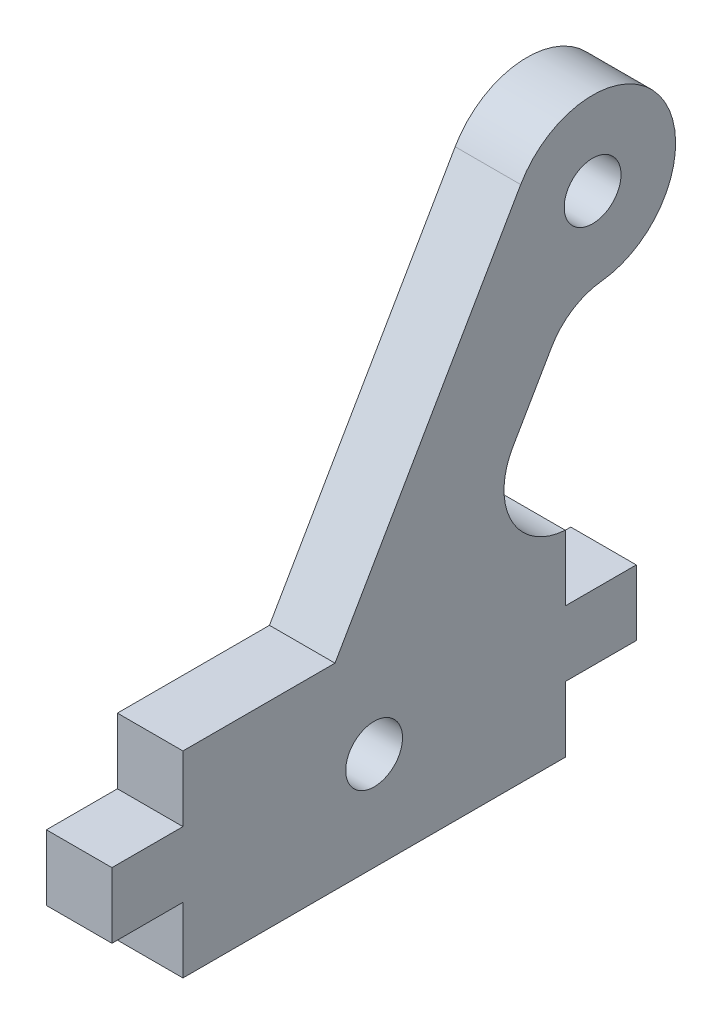
SolidWorks part; units mm, degrees
material "Acrílico (médio-alto impacto)"
ref_plane "Plano frontal" through (0, 0, 0) normal (0, 0, 1) x (1, 0, 0)
ref_plane "Plano superior" through (0, 0, 0) normal (0, 1, 0) x (1, 0, 0)
ref_plane "Plano direito" through (0, 0, 0) normal (1, 0, 0) x (0, 0, -1)
sketch "Principal" plane through (0, 0, 0) normal (1, 0, 0) x (0, 0, -1)
  line L0 (0, 0) -> (10, 17.3205) construction
  line L1 (-12, -1.5) -> (12, -1.5)
  line L2 (-12, -1.5) -> (-12, 1.5)
  line L3 (-12, 1.5) -> (12, 1.5)
  line L4 (12, -1.5) -> (12, 1.5)
  line L5 (0, 1.5) -> (0, -1.5) construction
  line L6 (-12, 0) -> (12, 0) construction
  line L11 (6.7091, 19.2205) -> (-1.7898, 4.5)
  line L12 (-8.75, 1.5) -> (-8.75, 4.5)
  line L13 (-8.75, -4.5) -> (8.75, -4.5)
  line L14 (-8.75, -4.5) -> (-8.75, -1.5)
  line L15 (-8.75, -1.5) -> (8.75, -1.5)
  line L16 (8.75, -4.5) -> (8.75, -1.5)
  line L17 (0, -1.5) -> (0, -4.5) construction
  line L18 (-8.75, -3) -> (8.75, -3) construction
  line L19 (-8.75, 4.5) -> (-1.7898, 4.5)
  line L20 (9.033, 13.6456) -> (3.7528, 4.5)
  line L21 (3.7528, 4.5) -> (8.75, 4.5)
  line L22 (8.75, 4.5) -> (8.75, 1.5)
  arc A0 (9.033, 13.6456) -> (6.7091, 19.2205) centre (10, 17.3205) ccw
  point P0 (0, 0)
  point P8 (0, -3)
  dimension "D6" = 3.8
  dimension "D8" = 25.6205
  dimension "D1" = 24
  dimension "D2" = 3
  dimension "D3" = 17.5
  dimension "D4" = 20
  dimension "D5" = 60
  dimension "D7" = 1
extrude "Base" add sketch "Principal" along normal blind 3 contours L3 | L1 L4 L3 L2 | L13 L16 L1 L14 region at (0, 0, 0) region at (0, -3, 0) region at (0, 9.7691, -4.3767)
hole_wizard "Furo de diâmetro Ø2.6 (2.6)1" positions "Esboço3" profile "Esboço4" hole size "Ø2.6" standard "ISO" end condition through all
sketch "Esboço3" plane through (3, 0, 0) normal (1, 0, 0) x (0, 0, -1)
  arc A0 (9.033, 13.6456) -> (6.7091, 19.2205) centre (10, 17.3205) ccw construction
  point P0 (0, 0)
  point P3 (10, 17.3205)
sketch "Esboço4" plane through (3, 0, 0) normal (0, 1, 0) x (0, 0, -1)
  line L0 (0, 0) -> (0, 3)
  line L1 (0, 3) -> (1.3, 3)
  line L2 (1.3, 3) -> (1.3, 0)
  line L5 (1.3, 0) -> (0, 0)
  line L11 (0, -6.35) -> (0, 107.95) construction
  dimension "Thru Hole Dia." = 2.6
  dimension "Thru Hole Depth" = 3
fillet "Filete1" radius 3 2 edges at (1.5, 4.5, -3.7528) (1.5, 13.6456, -9.033)
